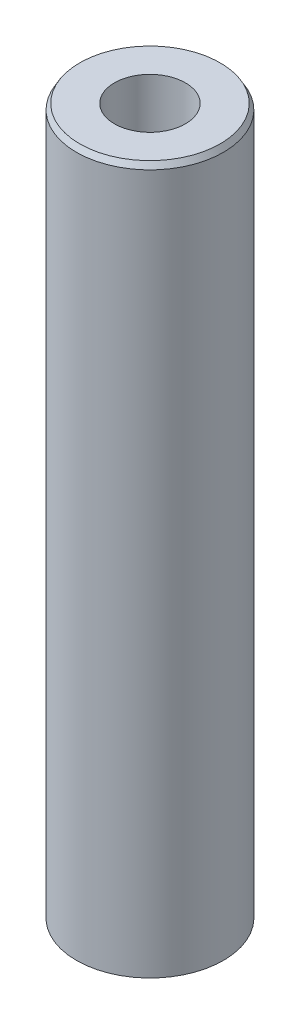
SolidWorks part; units mm, degrees
ref_plane "Front Plane" through (0, 0, 0) normal (0, 0, 1) x (1, 0, 0)
ref_plane "Top Plane" through (0, 0, 0) normal (0, 1, 0) x (1, 0, 0)
ref_plane "Right Plane" through (0, 0, 0) normal (1, 0, 0) x (0, 0, -1)
sketch "Sketch1" plane through (0, 0, 0) normal (0, 1, 0) x (1, 0, 0)
  circle A0 centre (0, 0) radius 60
  dimension "SHAFT_OD" = 120
extrude "Boss-Extrude1" add sketch "Sketch1" along normal blind 578.5926
sketch "Sketch2" plane through (0, 0, 0) normal (0, 1, 0) x (1, 0, 0)
  circle A0 centre (0, 0) radius 28.9984
  dimension "BORE_D" = 57.9969
extrude "Cut-Extrude1" cut sketch "Sketch2" along normal through all
chamfer "Chamfer1" distance 4.6429 angle 30 2 edges at (0, 578.5926, 60) (0, 0, 60) first distance on face at (0, 578.5926, 60) first distance on face at (0, 0, 28.9984)
